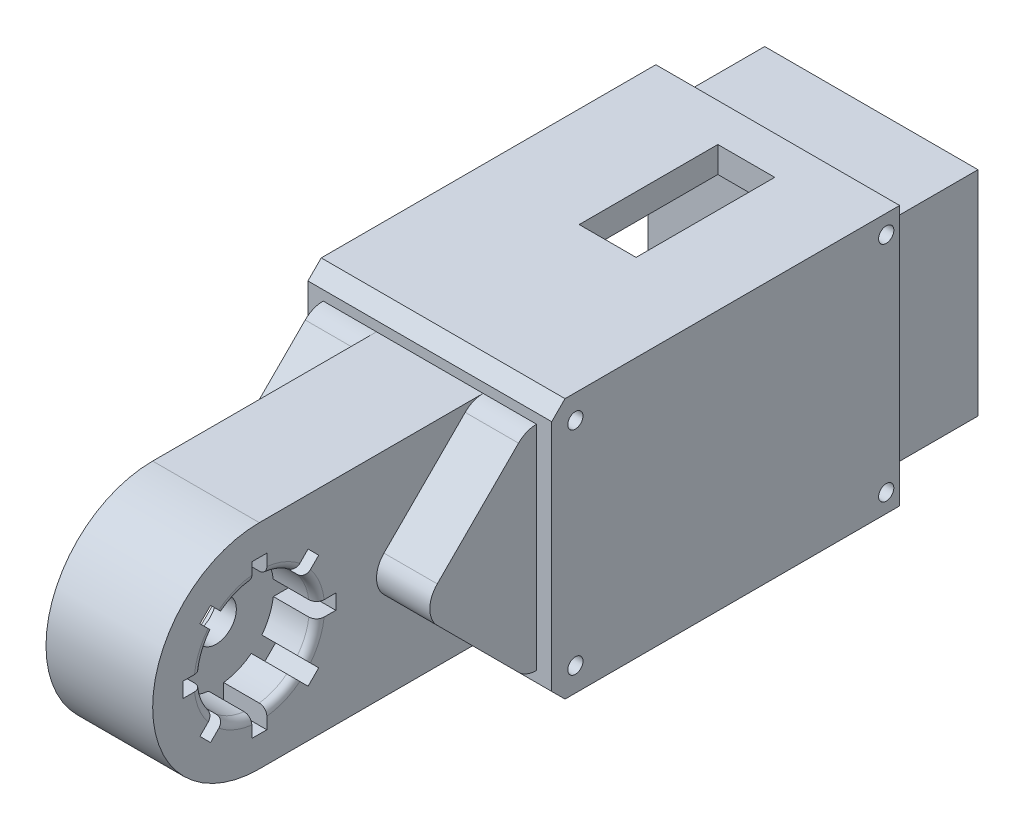
SolidWorks part; units mm, degrees
ref_plane "Front Plane" through (0, 0, 0) normal (0, 0, 1) x (1, 0, 0)
ref_plane "Top Plane" through (0, 0, 0) normal (0, 1, 0) x (1, 0, 0)
ref_plane "Right Plane" through (0, 0, 0) normal (1, 0, 0) x (0, 0, -1)
sketch "Sketch2" plane through (0, 0, 0) normal (0, 0, 1) x (1, 0, 0)
  line L1 (-21, 21) -> (21, 21)
  line L2 (-21, 21) -> (-21, -21)
  line L3 (-21, -21) -> (21, -21)
  line L4 (21, 21) -> (21, -21)
  line L5 (-21, 21) -> (21, -21) construction
  line L6 (-21, -21) -> (21, 21) construction
  point P0 (0, 0)
  dimension "D1" = 42
  dimension "D2" = 42
extrude "Boss-Extrude1" add sketch "Sketch2" along normal blind 89
ref_plane "Plane1" through (0, 0, 89) normal (0, 0, 1) x (1, 0, 0)
sketch "Sketch3" plane through (0, 0, 89) normal (0, 0, 1) x (1, 0, 0)
  line L0 (21, 21) -> (-21, 21) construction
  line L1 (10.5, -21) -> (-10.5, -21)
  line L2 (10.5, -21) -> (10.5, 21)
  line L3 (10.5, 21) -> (-10.5, 21)
  line L4 (-10.5, -21) -> (-10.5, 21)
  line L5 (10.5, -21) -> (-10.5, 21) construction
  line L6 (10.5, 21) -> (-10.5, -21) construction
  point P0 (0, 0)
  dimension "D1" = 21
ref_plane "Plane4" through (0, 0, 0) normal (0, 0, -1) x (-1, 0, 0)
extrude "Boss-Extrude2" add sketch "Sketch3" along normal blind 42
ref_plane "Plane5" through (-10.5, 0, 0) normal (-1, 0, 0) x (0, 0, 1)
sketch "Sketch8" plane through (-10.5, 0, 0) normal (-1, 0, 0) x (0, 0, 1)
  line L0 (131, 21) -> (131, -21) construction
  line L1 (131, 21) -> (131, -21)
  arc A0 (131, 21) -> (131, -21) centre (131, 0) cw
  dimension "D1" = 21
extrude "Boss-Extrude3" add sketch "Sketch8" against normal blind 21
ref_plane "Plane6" through (-10.5, 0, 0) normal (-1, 0, 0) x (0, 0, 1)
sketch "Sketch9" plane through (-10.5, 0, 0) normal (-1, 0, 0) x (0, 0, 1)
  line L0 (89, 21) -> (89, -21) construction
  line L1 (131, 21) -> (131, -21)
  circle A0 centre (131, 0) radius 11.35
  dimension "D1" = 42
  dimension "D2" = 22.7
extrude "Cut-Extrude2" cut sketch "Sketch9" against normal blind 8.5 contours A0
ref_plane "Plane7" through (10.5, 0, 0) normal (1, 0, 0) x (0, 0, -1)
sketch "Sketch11" plane through (10.5, 0, 0) normal (1, 0, 0) x (0, 0, -1)
  line L0 (-131, 21) -> (-131, -21)
  circle A0 centre (-131, 0) radius 11.35
  dimension "D1" = 22.7
extrude "Cut-Extrude3" cut sketch "Sketch11" against normal blind 8.5 contours A0
ref_plane "Plane8" through (-2, 0, 0) normal (-1, 0, 0) x (0, 0, 1)
sketch "Sketch12" plane through (-2, 0, 0) normal (-1, 0, 0) x (0, 0, 1)
  circle A0 centre (131, 0) radius 3.975
  dimension "D1" = 7.95
extrude "Cut-Extrude4" cut sketch "Sketch12" against normal through all
ref_plane "Plane10" through (-2, 0, 0) normal (-1, 0, 0) x (0, 0, 1)
ref_plane "Plane11" through (-10.5, 0, 0) normal (-1, 0, 0) x (0, 0, 1)
sketch "Sketch20" plane through (-10.5, 0, 0) normal (-1, 0, 0) x (0, 0, 1)
  line L0 (131, 0) -> (110, 0)
  line L1 (110, 0) -> (110, 21)
  line L2 (110, 0) -> (110, -21)
  line L4 (110, 21) -> (89, 21)
  line L6 (110, -21) -> (89, -21)
  line L7 (89, 21) -> (110, 0)
  line L8 (89, -21) -> (110, 0)
  line L9 (89, 21) -> (89, -21)
  circle A0 centre (131, 0) radius 11.35
  dimension "D1" = 21
extrude "Boss-Extrude4" add sketch "Sketch20" along normal blind 10.5 and the other way blind 31.5 contours L7 L9 L8 region at (-10.5, 0, 96)
fillet "Fillet1" radius 5 1 edges at (15.75, 0, 110)
fillet "Fillet2" radius 5 1 edges at (-15.75, 0, 110)
fillet "Fillet3" radius 5 1 edges at (-15.75, -21, 89)
fillet "Fillet4" radius 5 1 edges at (-15.75, 21, 89)
fillet "Fillet5" radius 5 1 edges at (15.75, -21, 89)
fillet "Fillet6" radius 5 1 edges at (15.75, 21, 89)
fillet "Fillet7" radius 1.5 1 edges at (-10.5, 0, 142.35)
fillet "Fillet8" radius 1.5 1 edges at (10.5, 0, 119.65)
sketch "Sketch21" plane through (-10.5, 0, 0) normal (-1, 0, 0) x (0, 0, 1)
  line L1 (129.5207, 10.6415) -> (132.4793, 10.6415)
  line L2 (129.5207, 10.6415) -> (129.5207, 15.0585)
  line L3 (129.5207, 15.0585) -> (132.4793, 15.0585)
  line L4 (132.4793, 10.6415) -> (132.4793, 15.0585)
  line L5 (129.5207, 10.6415) -> (132.4793, 15.0585) construction
  line L6 (129.5207, 15.0585) -> (132.4793, 10.6415) construction
  circle A0 centre (131, 0) radius 12.85 construction
  point P0 (131, 12.85)
  dimension "D1" = 4.417
extrude "Cut-Extrude5" cut sketch "Sketch21" against normal blind 8.5
pattern_circular "CirPattern2" count 8 over 360 about axis through (-9, 0, 131) along (-1, 0, 0) of "Cut-Extrude5"
ref_plane "Plane12" through (0, 21, 0) normal (0, 1, 0) x (1, 0, 0)
ref_plane "Plane13" through (10.5, 0, 0) normal (1, 0, 0) x (0, 0, -1)
ref_plane "Plane14" through (0, 0, 0) normal (1, 0, 0) x (0, 0, -1)
mirror "Mirror1" about plane through (0, 0, 0) normal (1, 0, 0) of "CirPattern2"
ref_plane "Plane15" through (21, 0, 0) normal (1, 0, 0) x (0, 0, -1)
sketch "Sketch24" plane through (21, 0, 0) normal (1, 0, 0) x (0, 0, -1)
  line L1 (-86.9289, 21) -> (0, 21)
  line L2 (-86.9289, 21) -> (-86.9289, 25.5452)
  line L3 (-86.9289, 25.5452) -> (0, 25.5452)
  line L4 (0, 21) -> (0, 25.5452)
  line L5 (-86.9289, -21) -> (0, -21)
  line L6 (-86.9289, -21) -> (-86.9289, -25.6891)
  line L7 (-86.9289, -25.6891) -> (0, -25.6891)
  line L8 (0, -21) -> (0, -25.6891)
extrude "Boss-Extrude6" add sketch "Sketch24" against normal blind 42
sketch "Sketch25" plane through (21, 0, 0) normal (1, 0, 0) x (0, 0, -1)
  line L0 (-18.4289, -25.6891) -> (-18.4289, 25.5452)
  line L1 (-86.9289, 25.5452) -> (-18.4289, 25.5452)
  line L2 (-86.9289, 25.5452) -> (-86.9289, -25.6891)
  line L3 (-86.9289, -25.6891) -> (-18.4289, -25.6891)
  dimension "D1" = 68.5
extrude "Boss-Extrude7" add sketch "Sketch25" along normal blind 3
ref_plane "Plane18" through (0, 0, 0) normal (0, 0, -1) x (-1, 0, 0)
ref_plane "Plane19" through (-21, 0, 0) normal (-1, 0, 0) x (0, 0, 1)
sketch "Sketch28" plane through (-21, 0, 0) normal (-1, 0, 0) x (0, 0, 1)
  line L0 (86.9289, -25.6891) -> (0, -25.6891) construction
  line L1 (86.9289, 25.5452) -> (18.4289, 25.5452)
  line L2 (86.9289, 25.5452) -> (86.9289, -25.6891)
  line L3 (86.9289, -25.6891) -> (18.4289, -25.6891)
  line L4 (18.4289, 25.5452) -> (18.4289, -25.6891)
  dimension "D1" = 68.5
extrude "Boss-Extrude8" add sketch "Sketch28" along normal blind 3
ref_plane "Plane20" through (-24, 0, 0) normal (-1, 0, 0) x (0, 0, 1)
sketch "Sketch30" plane through (-24, 0, 0) normal (-1, 0, 0) x (0, 0, 1)
  line L1 (81.9289, 20.4302) -> (19.9289, 20.4302)
  line L2 (81.9289, 20.4302) -> (81.9289, -20.5741)
  line L3 (81.9289, -20.5741) -> (19.9289, -20.5741)
  line L4 (19.9289, 20.4302) -> (19.9289, -20.5741)
  line L5 (81.9289, 20.4302) -> (19.9289, -20.5741) construction
  line L6 (81.9289, -20.5741) -> (19.9289, 20.4302) construction
  line L8 (86.9289, 25.5452) -> (18.4289, 25.5452) construction
  line L9 (18.4289, -25.6891) -> (86.9289, -25.6891) construction
  line L10 (86.9289, -21) -> (86.9289, 21) construction
  point P0 (50.9289, -0.0719)
  dimension "D1" = 5.115
  dimension "D2" = 5.115
  dimension "D3" = 62
  dimension "D4" = 5
extrude "Cut-Extrude6" cut sketch "Sketch30" against normal blind 45
ref_plane "Plane21" through (21, 0, 0) normal (1, 0, 0) x (0, 0, -1)
sketch "Sketch31" plane through (21, 0, 0) normal (1, 0, 0) x (0, 0, -1)
  line L0 (0, -25.6891) -> (0, 25.5452) construction
  line L1 (-18.4289, -25.6891) -> (0, -25.6891)
  line L2 (-18.4289, -25.6891) -> (-18.4289, -21.0741)
  line L3 (-18.4289, -21.0741) -> (0, -21.0741)
  line L4 (0, -25.6891) -> (0, -21.0741)
  line L6 (-18.4289, 25.5452) -> (0, 25.5452)
  line L7 (-18.4289, 25.5452) -> (-18.4289, 20.9302)
  line L8 (-18.4289, 20.9302) -> (0, 20.9302)
  line L9 (0, 25.5452) -> (0, 20.9302)
  dimension "D1" = 4.615
  dimension "D2" = 4.615
extrude "Cut-Extrude7" cut sketch "Sketch31" against normal through all
chamfer "Chamfer1" distance 1.5 angle 45 4 edges at (0, 20.9302, 18.4289) (21, -0.0719, 18.4289) (0, -21.0741, 18.4289) (-21, -0.0719, 18.4289)
ref_plane "Plane22" through (0, 0, 0) normal (0, 0, -1) x (-1, 0, 0)
sketch "Sketch32" plane through (0, 0, 0) normal (0, 0, -1) x (-1, 0, 0)
  line L1 (15, 15) -> (-15, 15)
  line L2 (15, 15) -> (15, -15)
  line L3 (15, -15) -> (-15, -15)
  line L4 (-15, 15) -> (-15, -15)
  line L5 (15, 15) -> (-15, -15) construction
  line L6 (15, -15) -> (-15, 15) construction
  point P0 (0, 0)
  dimension "D1" = 30
  dimension "D2" = 30
extrude "Cut-Extrude8" cut sketch "Sketch32" against normal blind 16.8
ref_plane "Plane23" through (0, 0, 19.9289) normal (0, 0, 1) x (1, 0, 0)
sketch "Sketch33" plane through (0, 0, 19.9289) normal (0, 0, 1) x (1, 0, 0)
  circle A0 centre (0, 0) radius 5
  dimension "D1" = 10
extrude "Cut-Extrude9" cut sketch "Sketch33" against normal blind 16.8
ref_plane "Plane24" through (-21, 0, 0) normal (-1, 0, 0) x (0, 0, 1)
sketch "Sketch34" plane through (-24, 0, 0) normal (-1, 0, 0) x (0, 0, 1)
  line L0 (86.9289, -0.0719) -> (103.6427, -0.0719) construction
  line L2 (88.3304, -21.6696) -> (88.3304, -28.2221)
  line L3 (88.3304, -28.2221) -> (81.7779, -28.2221)
  line L4 (81.7779, -28.2221) -> (88.3304, -21.6696)
  line L5 (86.9289, -25.6891) -> (86.9289, 25.5452) construction
  line L6 (88.3304, 28.0782) -> (81.7779, 28.0782)
  line L7 (88.3304, 21.5257) -> (88.3304, 28.0782)
  line L8 (81.7779, 28.0782) -> (88.3304, 21.5257)
extrude "Cut-Extrude10" cut sketch "Sketch34" against normal through all
chamfer "Chamfer2" distance 6 angle 45 1 edges at (-1.5, 20.4302, 81.9289)
chamfer "Chamfer3" distance 6 angle 45 1 edges at (-1.5, -20.5741, 81.9289)
chamfer "Chamfer4" distance 6 angle 45 1 edges at (-1.5, 20.4302, 19.9289)
chamfer "Chamfer5" distance 6 angle 45 1 edges at (-1.5, -20.5741, 19.9289)
sketch "Sketch35" plane through (-24, 0, 0) normal (-1, 0, 0) x (0, 0, 1)
  line L0 (78.9289, -17.5741) -> (85.6199, -24.3801) construction
  line L1 (82.2744, 20.8332) -> (85.6199, 24.2362) construction
  line L2 (81.9289, -14.5741) -> (75.9289, -20.5741) construction
  line L3 (84.3109, -25.6891) -> (86.9289, -23.0711) construction
  line L4 (78.9289, 17.4302) -> (85.6199, 24.2362) construction
  line L5 (75.9289, 20.4302) -> (81.9289, 14.4302) construction
  line L6 (86.9289, 22.9272) -> (84.3109, 25.5452) construction
  line L7 (18.4289, 25.5452) -> (21.0741, 21.9048) construction
  line L9 (18.4289, -25.6891) -> (21.074, -22.0485) construction
  line L10 (18.4289, 25.5452) -> (18.4289, -25.6891) construction
  circle A0 centre (21.0741, 21.9048) radius 1.5
  circle A1 centre (82.2744, 20.8332) radius 1.5
  circle A2 centre (82.2744, -20.9771) radius 1.5
  circle A3 centre (21.074, -22.0485) radius 1.5
  dimension "D5" = 3
  dimension "D1" = 36.003
  dimension "D2" = 36
  dimension "D3" = 4.5
  dimension "D4" = 4.5
extrude "Cut-Extrude11" cut sketch "Sketch35" against normal through all
ref_plane "Plane26" through (0, -25.6891, 0) normal (0, -1, 0) x (-1, 0, 0)
sketch "Sketch38" plane through (0, -25.6891, 0) normal (0, -1, 0) x (-1, 0, 0)
  line L0 (-24, -18.4289) -> (24, -18.4289) construction
  line L1 (4.2922, -53.2289) -> (-6.9078, -53.2289)
  line L2 (4.2922, -53.2289) -> (4.2922, -25.9289)
  line L3 (4.2922, -25.9289) -> (-6.9078, -25.9289)
  line L4 (-6.9078, -53.2289) -> (-6.9078, -25.9289)
  dimension "D1" = 7.5
  dimension "D2" = 27.3
  dimension "D3" = 11.2
extrude "Cut-Extrude12" cut sketch "Sketch38" against normal through all
sketch "Sketch39" plane through (0, 0, 0) normal (0, 0, 1) x (1, 0, 0)
  circle A0 centre (0, 0) radius 10.0263
